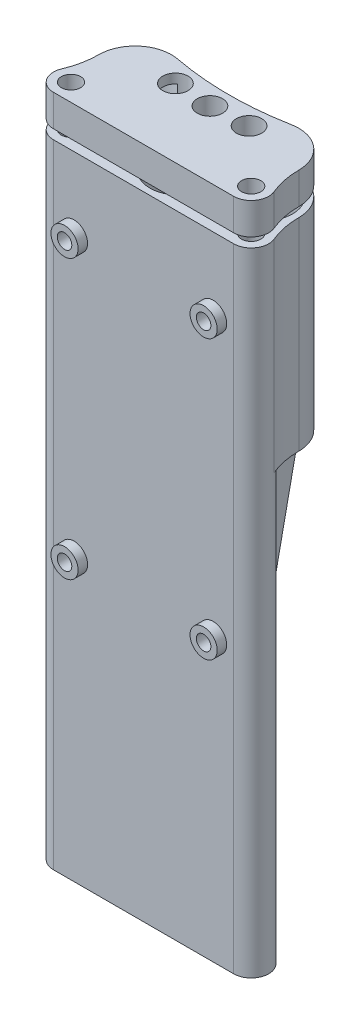
SolidWorks part; units mm, degrees
ref_plane "Front Plane" through (0, 0, 0) normal (0, 0, 1) x (1, 0, 0)
ref_plane "Top Plane" through (0, 0, 0) normal (0, 1, 0) x (1, 0, 0)
ref_plane "Right Plane" through (0, 0, 0) normal (1, 0, 0) x (0, 0, -1)
sketch "Sketch1" plane through (0, 0, 0) normal (0, 1, 0) x (1, 0, 0)
  line L0 (-28.5, 0) -> (28.5, 0) construction
  line L1 (-28.5, 0) -> (28.5, 0) construction
  line L2 (-28.5, 5.55) -> (28.5, 5.55)
  line L3 (-28.5, -5.55) -> (28.5, -5.55)
  circle A0 centre (-28.5, 0) radius 3.05
  circle A1 centre (28.5, 0) radius 3.05
  arc A2 (-28.5, 5.55) -> (-28.5, -5.55) centre (-28.5, 0) ccw
  arc A3 (28.5, -5.55) -> (28.5, 5.55) centre (28.5, 0) ccw
  point P4 (0, 0)
  dimension "D1" = 6.1
  dimension "D2" = 2.5
  dimension "D3" = 57
extrude "Boss-Extrude1" add sketch "Sketch1" along normal mid plane 200
sketch "Sketch2" plane through (0, 0, 0) normal (1, 0, 0) x (0, 0, -1)
  line L0 (5.55, 36.6649) -> (5.55, -0.5321)
  line L1 (5.55, 100) -> (5.55, -100) construction
  line L2 (5.55, -0.5321) -> (7.05, -0.5321)
  line L3 (7.05, -0.5321) -> (14.8208, 36.6649)
  line L4 (14.8208, 36.6649) -> (5.55, 36.6649)
  dimension "D1" = 11.8
  dimension "D2" = 38
  dimension "D3" = 1.5
extrude "Boss-Extrude2" add sketch "Sketch2" along normal up to vertex (28.5 mm away) and the other way up to vertex (28.5 mm away) up to point (28.5, 100, -5.55) other way up to point (-28.5, 100, -5.55)
sketch "Sketch3" plane through (0, -1.4335, -6.8617) normal (0, -0.2045, -0.9789) x (-1, 0, 0)
  line L0 (-14, 33.9209) -> (14, 5.9209) construction
  line L1 (0, 11.204) -> (0, -11.204) construction
  line L3 (-28.5, 0.9209) -> (-28.5, 38.9209) construction
  circle A0 centre (-14, 33.9209) radius 1.5
  circle A1 centre (-14, 5.9209) radius 1.5
  circle A2 centre (14, 33.9209) radius 1.5
  circle A3 centre (14, 5.9209) radius 1.5
  circle A4 centre (-14, 33.9209) radius 2.5
  circle A5 centre (14, 33.9209) radius 2.5
  circle A6 centre (14, 5.9209) radius 2.5
  circle A7 centre (-14, 5.9209) radius 2.5
  point P8 (0, 19.9209)
  point P13 (-28.5, 19.9209)
  dimension "D1" = 3
  dimension "D2" = 28
  dimension "D3" = 28
  dimension "D4" = 1
extrude "Boss-Extrude3" add sketch "Sketch3" along normal blind 1.5
chamfer "Chamfer1" distance 0.5 angle 45 4 edges at (14, 6.5027, -10.052) (-14, 6.5027, -10.052) (-14, 33.911, -15.7779) (14, 33.911, -15.7779)
sketch "Sketch6" plane through (0, 100, 0) normal (0, 1, 0) x (1, 0, 0)
  line L0 (-28.5, -5.55) -> (28.5, -5.55) construction
  line L3 (0, -17.5762) -> (0, 17.5762) construction
  line L4 (-28.5, -5.55) -> (28.5, -5.55)
  arc A0 (-3.9104, 14.6079) -> (3.9104, 14.6079) centre (0, 5.95) ccw
  arc A1 (-14.1587, 19.2894) -> (-10.6457, 12.3022) centre (-20.1375, 11.9067) ccw
  arc A2 (10.6457, 12.3022) -> (14.1587, 19.2894) centre (20.1375, 11.9067) ccw
  circle A4 centre (0, 5.95) radius 11.5 construction
  circle A6 centre (-20.1375, 11.9067) radius 11.5 construction
  circle A7 centre (20.1375, 11.9067) radius 11.5 construction
  circle A8 centre (-28.5, 0) radius 3.05 construction
  circle A10 centre (28.5, 0) radius 3.05 construction
  arc A11 (-31.6375, 11.9067) -> (-33.6123, 2.1604) centre (-56.6757, 11.9067) cw
  arc A12 (-28.5, 5.55) -> (-28.5, -5.55) centre (-28.5, 0) ccw construction
  arc A13 (-31.6375, 11.9067) -> (-17.9882, 23.2041) centre (-20.1375, 11.9067) cw
  arc A14 (31.6375, 11.9067) -> (17.9882, 23.2041) centre (20.1375, 11.9067) ccw
  arc A15 (31.6375, 11.9067) -> (33.6123, 2.1604) centre (56.6757, 11.9067) ccw
  arc A16 (28.5, -5.55) -> (28.5, 5.55) centre (28.5, 0) ccw construction
  arc A17 (-17.9882, 23.2041) -> (17.9882, 23.2041) centre (0, 117.7561) ccw
  arc A18 (-10.6457, 12.3022) -> (-14.1587, 19.2894) centre (-11.6498, 16.1741) ccw
  arc A19 (3.9104, 14.6079) -> (-3.9104, 14.6079) centre (0, 15.45) ccw
  arc A20 (14.1587, 19.2894) -> (10.6457, 12.3022) centre (11.6498, 16.1741) ccw
  circle A21 centre (-11.6498, 16.1741) radius 6 construction
  circle A22 centre (-11.6498, 16.1741) radius 4 construction
  circle A23 centre (-20.1375, 11.9067) radius 9.5 construction
  circle A24 centre (0, 5.95) radius 9.5 construction
  circle A25 centre (20.1375, 11.9067) radius 9.5 construction
  arc A26 (-33.6123, 2.1604) -> (-28.5, -5.55) centre (-28.5, 0) ccw
  arc A27 (33.6123, 2.1604) -> (28.5, -5.55) centre (28.5, 0) cw
  circle A28 centre (-28.5, 0) radius 3.05
  circle A29 centre (28.5, 0) radius 3.05
  line M6 (28.5, 5.55) -> (-28.5, 5.55)
  dimension "D1" = 19
  dimension "D4" = 8
  dimension "D2" = 2
  dimension "D3" = 2
  dimension "D5" = 2
extrude "Boss-Extrude5" add sketch "Sketch6" against normal blind 60
extrude "Cut-Extrude2" cut sketch "Sketch6<2>" against normal up to surface (60 mm away) contours A1 M6 | A0 M6 | A2 M6 region at (20.1375, 100, -4.273) region at (-20.1375, 100, -4.273) region at (0, 100, -1.7011) up to face at (0, 40, -11.9943)
sketch "Sketch6<2>" plane through (0, 100, 0) normal (0, 1, 0) x (1, 0, 0) same geometry as "Sketch6"
sketch "Sketch7" plane through (0, 40, 0) normal (0, -1, 0) x (1, 0, 0)
  line L0 (-28.5, -5.55) -> (28.5, -5.55)
  line L4 (-9.4916, -5.55) -> (-13.0776, -5.55)
  line L5 (-27.1973, -5.55) -> (-28.5, -5.55)
  line L6 (28.5, -5.55) -> (27.1973, -5.55)
  line L7 (13.0776, -5.55) -> (9.4916, -5.55)
  arc A16 (-10.6457, -12.3022) -> (-13.0776, -5.55) centre (-20.1375, -11.9067) ccw
  arc A17 (-14.1587, -19.2894) -> (-10.6457, -12.3022) centre (-11.6498, -16.1741) ccw
  arc A18 (-27.1973, -5.55) -> (-14.1587, -19.2894) centre (-20.1375, -11.9067) ccw
  arc A20 (-31.6375, -11.9067) -> (-33.6123, -2.1604) centre (-56.6757, -11.9067) ccw
  arc A21 (-31.6375, -11.9067) -> (-17.9882, -23.2041) centre (-20.1375, -11.9067) ccw
  arc A22 (17.9882, -23.2041) -> (-17.9882, -23.2041) centre (0, -117.7561) ccw
  arc A23 (17.9882, -23.2041) -> (31.6375, -11.9067) centre (20.1375, -11.9067) ccw
  arc A24 (33.6123, -2.1604) -> (31.6375, -11.9067) centre (56.6757, -11.9067) ccw
  arc A26 (14.1587, -19.2894) -> (27.1973, -5.55) centre (20.1375, -11.9067) ccw
  arc A27 (10.6457, -12.3022) -> (14.1587, -19.2894) centre (11.6498, -16.1741) ccw
  arc A28 (13.0776, -5.55) -> (10.6457, -12.3022) centre (20.1375, -11.9067) ccw
  arc A29 (3.9104, -14.6079) -> (9.4916, -5.55) centre (0, -5.95) ccw
  arc A30 (-3.9104, -14.6079) -> (3.9104, -14.6079) centre (0, -15.45) ccw
  arc A31 (-9.4916, -5.55) -> (-3.9104, -14.6079) centre (0, -5.95) ccw
  arc A36 (-31.6375, -11.9067) -> (-33.6123, -2.1604) centre (-56.6757, -11.9067) ccw
  arc A37 (-31.6375, -11.9067) -> (-17.9882, -23.2041) centre (-20.1375, -11.9067) ccw
  arc A38 (17.9882, -23.2041) -> (-17.9882, -23.2041) centre (0, -117.7561) ccw
  arc A39 (17.9882, -23.2041) -> (31.6375, -11.9067) centre (20.1375, -11.9067) ccw
  arc A40 (33.6123, -2.1604) -> (31.6375, -11.9067) centre (56.6757, -11.9067) ccw
  arc A48 (-33.6123, -2.1604) -> (-28.5, -5.55) centre (-28.5, 0) ccw
  arc A49 (-33.6123, -2.1604) -> (-28.5, -5.55) centre (-28.5, 0) ccw
  arc A50 (28.5, -5.55) -> (33.6123, -2.1604) centre (28.5, 0) ccw
  arc A51 (28.5, -5.55) -> (33.6123, -2.1604) centre (28.5, 0) ccw
  dimension "D1" = 0
extrude "Boss-Extrude6" add sketch "Sketch7" along normal blind 4
extrude "Boss-Extrude7" add sketch "Sketch6<3>" along normal blind 7 from offset 3 separate body
sketch "Sketch6<3>" plane through (0, 100, 0) normal (0, 1, 0) x (1, 0, 0) same geometry as "Sketch6"
sketch "Sketch9" plane through (0, 110, 0) normal (0, 1, 0) x (1, 0, 0)
  line L1 (-28.5, -5.55) -> (28.5, -5.55)
  line L2 (-28.5, -5.55) -> (28.5, -5.55)
  circle A0 centre (-11.6498, 16.1741) radius 4
  circle A1 centre (0, 15.45) radius 4
  circle A2 centre (11.6498, 16.1741) radius 4
  arc A3 (14.1587, 19.2894) -> (10.6457, 12.3022) centre (11.6498, 16.1741) ccw construction
  arc A4 (3.9104, 14.6079) -> (-3.9104, 14.6079) centre (0, 15.45) ccw construction
  arc A5 (-10.6457, 12.3022) -> (-14.1587, 19.2894) centre (-11.6498, 16.1741) ccw construction
  circle A6 centre (28.5, 0) radius 3.05 construction
  arc A7 (-17.9882, 23.2041) -> (-31.6375, 11.9067) centre (-20.1375, 11.9067) ccw
  arc A8 (-33.6123, 2.1604) -> (-31.6375, 11.9067) centre (-56.6757, 11.9067) ccw
  arc A9 (-33.6123, 2.1604) -> (-28.5, -5.55) centre (-28.5, 0) ccw
  arc A10 (28.5, -5.55) -> (33.6123, 2.1604) centre (28.5, 0) ccw
  arc A11 (31.6375, 11.9067) -> (33.6123, 2.1604) centre (56.6757, 11.9067) ccw
  arc A12 (31.6375, 11.9067) -> (17.9882, 23.2041) centre (20.1375, 11.9067) ccw
  arc A13 (-17.9882, 23.2041) -> (17.9882, 23.2041) centre (0, 117.7561) ccw
  arc A14 (-17.9882, 23.2041) -> (-31.6375, 11.9067) centre (-20.1375, 11.9067) ccw
  arc A15 (-33.6123, 2.1604) -> (-31.6375, 11.9067) centre (-56.6757, 11.9067) ccw
  arc A16 (-33.6123, 2.1604) -> (-28.5, -5.55) centre (-28.5, 0) ccw
  arc A17 (28.5, -5.55) -> (33.6123, 2.1604) centre (28.5, 0) ccw
  arc A18 (31.6375, 11.9067) -> (33.6123, 2.1604) centre (56.6757, 11.9067) ccw
  arc A19 (31.6375, 11.9067) -> (17.9882, 23.2041) centre (20.1375, 11.9067) ccw
  arc A20 (-17.9882, 23.2041) -> (17.9882, 23.2041) centre (0, 117.7561) ccw
  circle A21 centre (-28.5, 0) radius 3.05 construction
  circle A22 centre (28.5, 0) radius 3.05
  circle A23 centre (-28.5, 0) radius 3.05
  dimension "D1" = 0
extrude "Boss-Extrude8" add sketch "Sketch9" along normal blind 3
sketch "Sketch4" plane through (0, 0, 5.55) normal (0, 0, 1) x (1, 0, 0)
  line L0 (0, -17.5762) -> (0, 17.5762) construction
  line L1 (-26, 100) -> (26, 100) construction
  line L2 (-26, 100) -> (-26, -15) construction
  line L3 (-26, -15) -> (26, -15) construction
  line L4 (26, 100) -> (26, -15) construction
  line L5 (-28.5, 100) -> (28.5, 100) construction
  line L6 (-22, 77) -> (22, 77) construction
  line L7 (-22, -11) -> (22, -11) construction
  circle A0 centre (-22, 77) radius 2.3
  circle A1 centre (22, 77) radius 2.3
  circle A2 centre (-22, -11) radius 2.3
  circle A3 centre (22, -11) radius 2.3
  circle A4 centre (-22, 77) radius 4.3
  circle A5 centre (22, 77) radius 4.3
  circle A6 centre (-22, -11) radius 4.3
  circle A7 centre (22, -11) radius 4.3
  point P4 (0, 100)
  point P12 (0, 77)
  point P16 (0, -11)
  dimension "D7" = 4.6
  dimension "D1" = 52
  dimension "D2" = 115
  dimension "D3" = 23
  dimension "D4" = 4
  dimension "D5" = 4
  dimension "D6" = 4
  dimension "D8" = 2
extrude "Boss-Extrude4" add sketch "Sketch4" along normal blind 3
extrude "Cut-Extrude1" cut sketch "Sketch4<2>" against normal blind 3 contours A1 | A0 | A3 | A2 region at (-22, 77, 5.55) region at (22, 77, 5.55) region at (-22, -11, 5.55) region at (22, -11, 5.55)
sketch "Sketch4<2>" plane through (0, 0, 5.55) normal (0, 0, 1) x (1, 0, 0) same geometry as "Sketch4"
